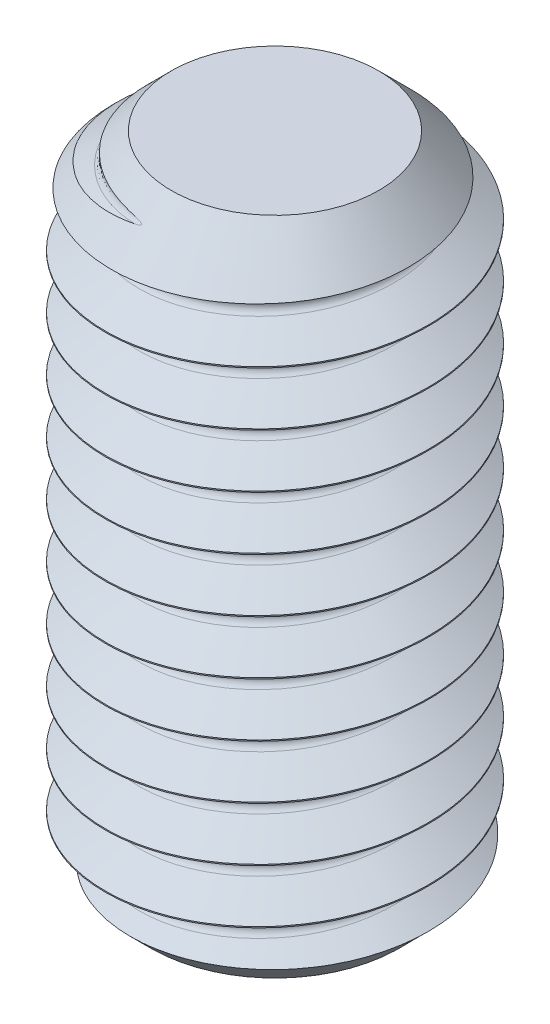
SolidWorks part; units mm, degrees
ref_plane "Front Plane" through (0, 0, 0) normal (0, 0, 1) x (1, 0, 0)
ref_plane "Top Plane" through (0, 0, 0) normal (0, 1, 0) x (1, 0, 0)
ref_plane "Right Plane" through (0, 0, 0) normal (1, 0, 0) x (0, 0, -1)
sketch "Sketch1" plane through (0, 0, 0) normal (0, 1, 0) x (1, 0, 0)
  circle A0 centre (0, 0) radius 3
  dimension "D1" = 6
extrude "Boss-Extrude1" add sketch "Sketch1" along normal mid plane 13.17
sketch "Sketch2" plane through (0, 0, 0) normal (0, 0, 1) x (1, 0, 0)
  line L0 (0.75, 6.585) -> (5.9507, 1.3843)
  line L1 (5.9507, 1.3843) -> (5.9507, -2.9343)
  line L2 (5.9507, -2.9343) -> (2.3, -6.585)
  line L3 (2.3, -6.585) -> (2.3, -11.4405)
  line L4 (2.3, -11.4405) -> (9.8714, -11.4405)
  line L5 (9.8714, -11.4405) -> (9.8714, 12.2044)
  line L6 (9.8714, 12.2044) -> (0.75, 12.2044)
  line L7 (0.75, 12.2044) -> (0.75, 6.585)
  line L8 (0, 0) -> (0, -3.1523) construction
  line L9 (3, 6.585) -> (-3, 6.585) construction
  line L10 (-3, -6.585) -> (3, -6.585) construction
  dimension "D1" = 1.5
  dimension "D2" = 4.6
  dimension "D3" = 135
  dimension "D4" = 135
revolve "Cut-Revolve1" cut sketch "Sketch2" angle 360 about L8
sketch "Sketch3" plane through (0, -6.585, 0) normal (0, -1, 0) x (1, 0, 0)
  line L1 (1.54, -0.8891) -> (1.54, 0.8891)
  line L2 (1.54, 0.8891) -> (0, 1.7782)
  line L3 (0, 1.7782) -> (-1.54, 0.8891)
  line L4 (-1.54, 0.8891) -> (-1.54, -0.8891)
  line L5 (-1.54, -0.8891) -> (0, -1.7782)
  line L6 (0, -1.7782) -> (1.54, -0.8891)
  circle A0 centre (0, 0) radius 1.54 construction
  dimension "D1" = 3.08
extrude "Cut-Extrude1" cut sketch "Sketch3" against normal blind 2.5
sketch "Sketch4" plane through (0, -6.585, 0) normal (0, -1, 0) x (1, 0, 0)
  circle A0 centre (0, 0) radius 3 construction
  circle A1 centre (0, 0) radius 3
curve "Helix/Spiral1" pitch 1 height 14.5 radius 3 centre (0, -6.585, 0) axis (0, 1, 0) start towards (0, 0, -1)
sketch "Sketch5" plane through (0, 0, 0) normal (0, 0, 1) x (1, 0, 0)
  line L1 (3.0097, -6.1477) -> (2.3688, -6.5177)
  line L2 (2.3688, -6.7677) -> (3.0097, -7.1377)
  line L3 (3.0097, -7.1377) -> (3.0097, -6.1477)
  circle A0 centre (2.7239, -6.6427) radius 0.2858 construction
  arc A1 (2.3688, -6.5177) -> (2.3688, -6.7677) centre (2.4409, -6.6427) ccw
  dimension "D2" = 0.1443
  dimension "D1" = 0.99
sweep "Cut-Sweep1" cut profiles "Sketch5" path "Helix/Spiral1" align with end faces yes
sketch "Sketch6" plane through (0, -6.585, 0) normal (0, -1, 0) x (1, 0, 0)
  circle A0 centre (0, 0) radius 1.7782
extrude "Cut-Extrude2" cut sketch "Sketch6" against normal blind 1.5 draft 75
sketch "Sketch7" plane through (0, 0, 0) normal (0, 0, 1) x (1, 0, 0)
  line L0 (-3, 3.3679) -> (-3, -6.3959) construction
sketch "Sketch8" plane through (0, 0, 0) normal (0, 0, 1) x (1, 0, 0)
  line L0 (-1.925, 5.41) -> (1.925, 5.41)
  line L1 (-0.75, 6.585) -> (-2.3589, 4.9761) construction
  line L2 (2.6756, 4.6594) -> (0.75, 6.585) construction
  line L3 (1.925, 5.41) -> (1.925, 7.1471)
  line L4 (1.925, 7.1471) -> (-1.925, 7.1471)
  line L5 (-1.925, 7.1471) -> (-1.925, 5.41)
  dimension "D1" = 3.85
extrude "Cut-Extrude3" cut sketch "Sketch8" against normal through all both and the other way through all
sketch "Sketch9" plane through (0, 0, 0) normal (0, 0, 1) x (1, 0, 0)
  line L0 (0, -6.585) -> (0, 5.41) construction
  line L1 (-2.3, -6.585) -> (2.3, -6.585) construction
  line L2 (1.925, 5.41) -> (-1.925, 5.41) construction
